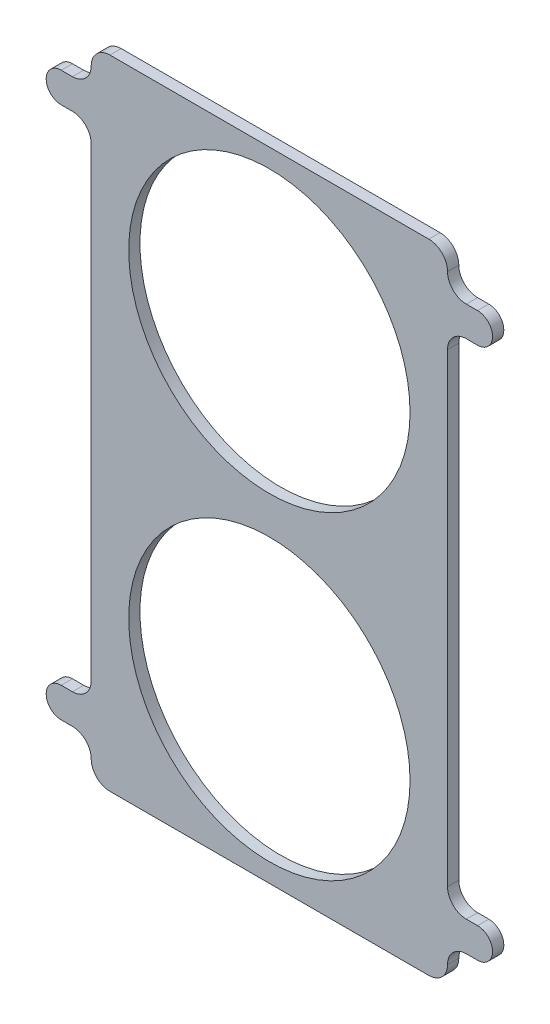
SolidWorks part; units mm, degrees
ref_plane "前基準面" through (0, 0, 0) normal (0, 0, 1) x (1, 0, 0)
ref_plane "上基準面" through (0, 0, 0) normal (0, 1, 0) x (1, 0, 0)
ref_plane "右基準面" through (0, 0, 0) normal (1, 0, 0) x (0, 0, -1)
ref_axis "基準軸1" through (0, -55, 0) along (0, 1, 0)
ref_axis "基準軸2" through (-88.99, 0, 0) along (1, 0, 0)
ref_axis "基準軸3" through (0, 0, 55) along (0, 0, -1)
sketch "草圖1" plane through (0, 0, 0) normal (0, 0, 1) x (1, 0, 0)
  line L0 (-47.5, 67) -> (-47.5, -67)
  line L1 (-47.5, 85) -> (47.5, 85)
  line L2 (-47.5, 85) -> (-47.5, 75)
  line L3 (-47.5, -85) -> (47.5, -85)
  line L4 (47.5, 85) -> (47.5, 75)
  line L5 (55, 0) -> (-55, 0) construction
  line L6 (0, -55) -> (0, 55) construction
  line L7 (55.5, 75) -> (47.5, 75)
  line L8 (55.5, 67) -> (47.5, 67)
  line L9 (47.5, 67) -> (47.5, -67)
  line L10 (55.5, -67) -> (47.5, -67)
  line L11 (55.5, -75) -> (47.5, -75)
  line L12 (-55.5, -75) -> (-47.5, -75)
  line L13 (-55.5, -67) -> (-47.5, -67)
  line L14 (-55.5, 67) -> (-47.5, 67)
  line L15 (-55.5, 75) -> (-47.5, 75)
  line L16 (-47.5, -75) -> (-47.5, -85)
  line L17 (47.5, -75) -> (47.5, -85)
  arc A4 (55.5, 67) -> (55.5, 75) centre (55.5, 71) ccw
  arc A5 (55.5, -67) -> (55.5, -75) centre (55.5, -71) cw
  arc A6 (-55.5, -67) -> (-55.5, -75) centre (-55.5, -71) ccw
  arc A7 (-55.5, 67) -> (-55.5, 75) centre (-55.5, 71) cw
  dimension "D1" = 95
  dimension "D2" = 170
  dimension "D3" = 85
  dimension "D4" = 47.5
  dimension "D5" = 8
  dimension "D6" = 8
  dimension "D7" = 10
extrude "填料-伸長1" add sketch "草圖1" along normal blind 3
fillet "圓角1" radius 5 12 edges at (-47.5, -67, 1.5) (-47.5, -75, 1.5) (-47.5, 67, 1.5) (-47.5, 75, 1.5) (47.5, 67, 1.5) (47.5, 75, 1.5) (47.5, -67, 1.5) (47.5, -75, 1.5) (47.5, -85, 1.5) (-47.5, -85, 1.5) (-47.5, 85, 1.5) (47.5, 85, 1.5)
sketch "草圖2" plane through (0, 0, 3) normal (0, 0, 1) x (1, 0, 0)
  line L0 (0, -55) -> (0, 55) construction
  line L1 (55, 0) -> (-55, 0) construction
  circle A0 centre (0, 42.5) radius 37.5
  circle A1 centre (0, -42.5) radius 37.5
  dimension "D1" = 75
  dimension "D2" = 42.5
extrude "除料-伸長1" cut sketch "草圖2" against normal up to next
